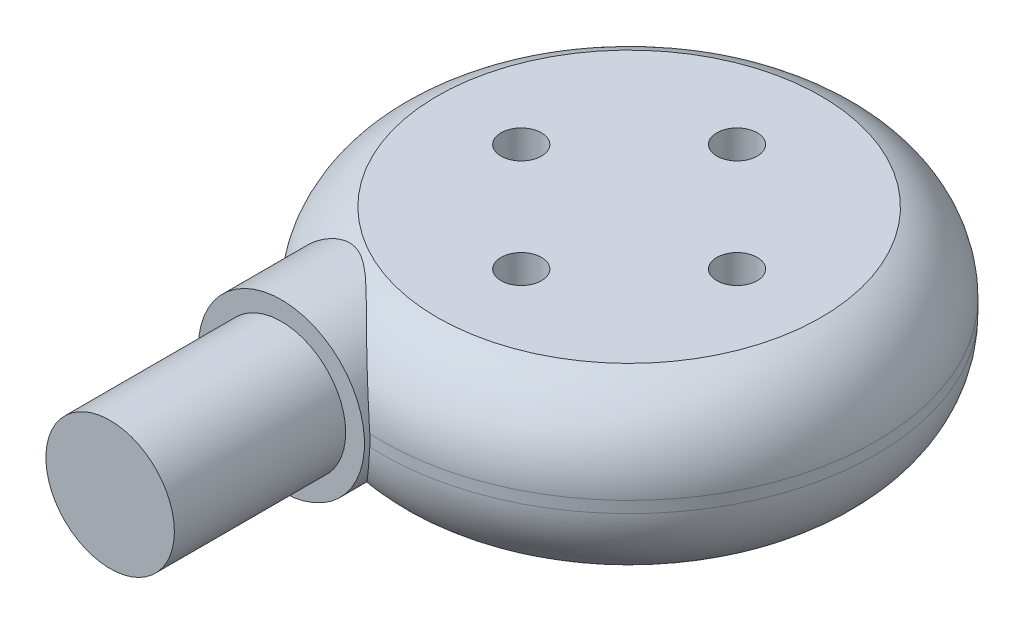
SolidWorks part; units mm, degrees
ref_plane "Front Plane" through (0, 0, 0) normal (0, 0, 1) x (1, 0, 0)
ref_plane "Top Plane" through (0, 0, 0) normal (0, 1, 0) x (1, 0, 0)
ref_plane "Right Plane" through (0, 0, 0) normal (1, 0, 0) x (0, 0, -1)
sketch "Sketch1" plane through (0, 0, 0) normal (0, 0, 1) x (1, 0, 0)
  circle A0 centre (0, 0) radius 6.1595 construction
  circle A1 centre (0, 0) radius 4.7625
  dimension "D1" = 12.319
  dimension "D2" = 9.525
extrude "Boss-Extrude1" add sketch "Sketch1" along normal blind 12.7
sketch "Sketch2" plane through (0, 0, 0) normal (0, 0, -1) x (-1, 0, 0)
  circle A0 centre (0, 0) radius 6.1595
extrude "Boss-Extrude2" add sketch "Sketch2" along normal blind 6.35
sketch "Sketch3" plane through (0, 0, 0) normal (0, 1, 0) x (1, 0, 0)
  line L0 (0, 6.35) -> (7.112, 18.6683) construction
  line L1 (6.1595, 6.35) -> (-6.1595, 6.35) construction
  circle A0 centre (7.112, 18.6683) radius 14.224
  circle A3 centre (7.112, 18.6683) radius 18.288
  dimension "D3" = 4.064
  dimension "D1" = 120
  dimension "D2" = 14.224
extrude "Boss-Extrude3" add sketch "Sketch3" along normal blind 6.35 and the other way blind 6.35
sketch "Sketch4" plane through (0, 6.35, 0) normal (0, 1, 0) x (1, 0, 0)
  circle A0 centre (7.112, 18.6683) radius 14.224
  circle A1 centre (7.112, 18.6683) radius 14.224 construction
extrude "Cut-Extrude1" cut sketch "Sketch4" against normal through all
fillet "Fillet1" radius 6.35 2 edges at (7.112, -6.35, -0.3803) (7.112, 6.35, -0.3803)
sketch "Sketch5" plane through (0, 0, 0) normal (0, 1, 0) x (1, 0, 0)
  circle A0 centre (7.112, 18.6683) radius 14.224
extrude "Boss-Extrude4" add sketch "Sketch5" along normal blind 2.54 from offset 3.81
sketch "Sketch6" plane through (0, 3.81, 0) normal (0, -1, 0) x (1, 0, 0)
  circle A0 centre (-0.888, -18.6683) radius 1.5
  circle A1 centre (15.112, -18.6683) radius 1.5
  circle A2 centre (7.112, -10.6683) radius 1.5
  circle A3 centre (7.112, -26.6683) radius 1.5
  circle A4 centre (7.112, -18.6683) radius 14.224 construction
  point P8 (0, 0)
  point P11 (7.112, -18.6683)
  point P12 (0, 0)
  point P14 (0, 0)
  point P15 (0, 0)
  point P16 (15.112, -18.6683)
  dimension "D1" = 3
  dimension "D2" = 16
  dimension "D3" = 16
  dimension "D4" = 8
  dimension "D5" = 8
  dimension "D6" = 8
extrude "Cut-Extrude2" cut sketch "Sketch6" against normal through all
